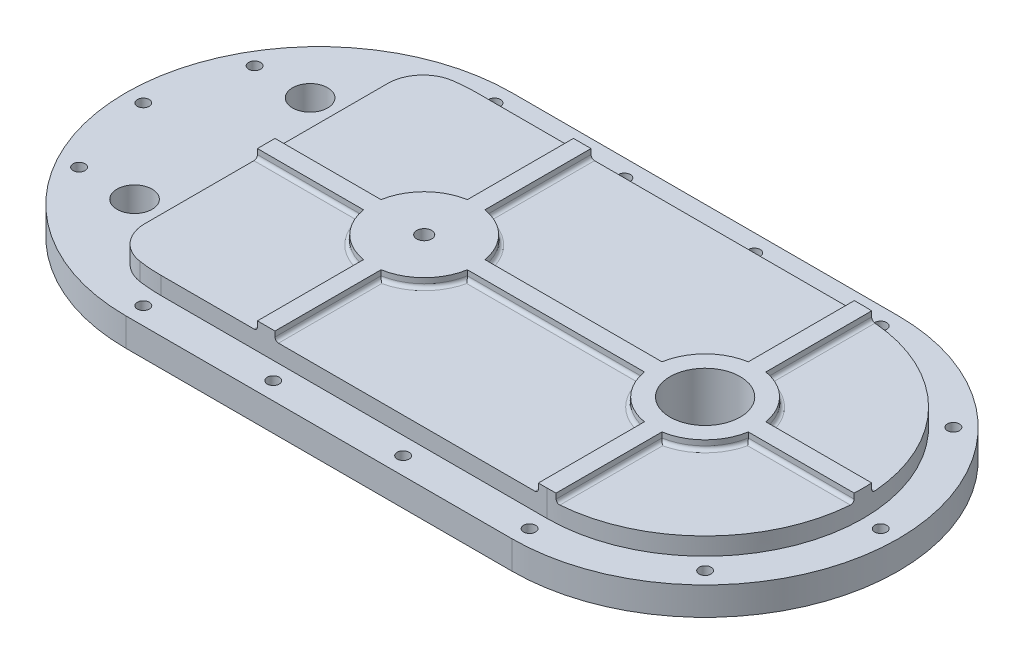
SolidWorks part; units mm, degrees
ref_plane "Front Plane" through (0, 0, 0) normal (0, 0, 1) x (1, 0, 0)
ref_plane "Top Plane" through (0, 0, 0) normal (0, 1, 0) x (1, 0, 0)
ref_plane "Right Plane" through (0, 0, 0) normal (1, 0, 0) x (0, 0, -1)
sketch "Sketch1" plane through (0, 0, 0) normal (0, 1, 0) x (1, 0, 0)
  line L0 (0, 0) -> (220, 0) construction
  line L1 (0, 110) -> (220, 110)
  line L2 (0, -110) -> (220, -110)
  arc A0 (0, 110) -> (0, -110) centre (0, 0) ccw
  arc A1 (220, -110) -> (220, 110) centre (220, 0) ccw
  point P3 (110, 0)
  dimension "D2" = 110
  dimension "D1" = 220
extrude "Boss-Extrude1" add sketch "Sketch1" along normal blind 16
sketch "Sketch2" plane through (0, 16, 0) normal (0, 1, 0) x (1, 0, 0)
  line L2 (0, 0) -> (-30, 0)
  line L3 (-30, -69.282) -> (-30, 69.282)
  line L4 (0, -90) -> (220, -90)
  line L5 (220, 90) -> (0, 90)
  line L6 (0, -90) -> (220, -90)
  line L7 (220, 90) -> (0, 90)
  arc A0 (-12.8571, -89.0769) -> (0, -90) centre (0, 0) ccw
  arc A1 (-30, -69.282) -> (-12.8571, -89.0769) centre (-10, -69.282) ccw
  arc A2 (-30, 69.282) -> (-12.8571, 89.0769) centre (-10, 69.282) cw
  arc A4 (0, 90) -> (0, -90) centre (0, 0) ccw
  arc A5 (220, -90) -> (220, 90) centre (220, 0) ccw
  arc A6 (0, 90) -> (-12.8571, 89.0769) centre (0, 0) ccw
  arc A7 (220, -90) -> (220, 90) centre (220, 0) ccw
  point P3 (-30, 0)
  point P6 (-30, -84.8528)
  dimension "D3" = 20
  dimension "D2" = 30
  dimension "D1" = 20
extrude "Boss-Extrude2" add sketch "Sketch2" along normal blind 10 contours L6 A7 L7 A6 A2 L3 A1 A0 region at (131.5227, 16, 0)
sketch "Sketch4" plane through (0, 26, 0) normal (0, 1, 0) x (1, 0, 0)
  line L0 (-30, 0) -> (310, 0) construction
  line L1 (-30, -69.282) -> (-30, 69.282) construction
  line L2 (0, 0) -> (60, 0) construction
  line L3 (60, 0) -> (220, 0) construction
  line L4 (60, -90) -> (60, 90) construction
  line L5 (0, -90) -> (220, -90) construction
  line L6 (220, 90) -> (0, 90) construction
  line L7 (220, 90) -> (220, -90) construction
  line L8 (-30, -5) -> (30.4196, -5)
  line L9 (65, -90) -> (65, -29.5804)
  line L10 (215, 90) -> (215, 29.5804)
  line L11 (-30, 5) -> (30.4196, 5)
  line L12 (55, -90) -> (55, -29.5804)
  line L13 (225, 90) -> (225, 29.5804)
  line L14 (89.5804, 5) -> (190.4196, 5)
  line L15 (-30, 5) -> (310, 5) construction
  line L16 (55, 29.5804) -> (55, 90)
  line L17 (55, -90) -> (55, 90) construction
  line L18 (89.5804, -5) -> (190.4196, -5)
  line L19 (-30, -5) -> (310, -5) construction
  line L20 (65, 29.5804) -> (65, 90)
  line L21 (65, -90) -> (65, 90) construction
  line L22 (249.5804, 5) -> (310, 5)
  line L23 (215, -29.5804) -> (215, -90)
  line L24 (215, 90) -> (215, -90) construction
  line L25 (225, -29.5804) -> (225, -90)
  line L26 (225, 90) -> (225, -90) construction
  line L27 (249.5804, -5) -> (310, -5)
  arc A0 (220, -90) -> (220, 90) centre (220, 0) ccw construction
  arc A1 (220, -90) -> (220, 90) centre (220, 0) ccw construction
  circle A2 centre (220, 0) radius 30
  circle A3 centre (60, 0) radius 30
  line M9 (-30, 69.282) -> (-30, -69.282)
  line M12 (0, -90) -> (220, -90)
  arc M13 (220, -90) -> (220, 90) centre (220, 0) ccw
  line M14 (220, 90) -> (0, 90)
  dimension "D5" = 60
  dimension "D6" = 60
  dimension "D1" = 60
  dimension "D2" = 160
  dimension "D3" = 5
  dimension "D4" = 5
extrude "Boss-Extrude3" add sketch "Sketch4" along normal blind 5 contours A3 L11 L8 M9 | A3 | A3 L20 L16 M14 | A3 L12 L9 M12 | A3 L18 A2 L14 | A2 | A2 L13 L10 M13 M14 | A2 L27 L22 M13 | A2 L23 L25 M12 M13 region at (0.0699, 26, 0) region at (60, 26, 0) region at (60, 26, 59.9301) region at (60, 26, -59.9301) region at (140, 26, 0) region at (219.9986, 26, 59.9186) region at (220, 26, 0) region at (219.9986, 26, -59.9186) region at (279.907, 26, 0)
sketch "Sketch5" plane through (0, 31, 0) normal (0, 1, 0) x (1, 0, 0)
  line L0 (0, 0) -> (220, 0) construction
  circle A0 centre (220, 0) radius 20
  dimension "D1" = 40
extrude "Cut-Extrude1" cut sketch "Sketch5" against normal through all
fillet "Fillet1" radius 2 22 edges at (55, 26, -59.7902) (38.7868, 26, -21.2132) (0.2098, 26, -5) (215, 26, -59.7902) (198.7868, 26, -21.2132) (65, 26, -59.7902) (81.2132, 26, -21.2132) (140, 26, -5) (279.7207, 26, -5) (225, 26, -59.7207) (241.2132, 26, -21.2132) (279.7207, 26, 5) (241.2132, 26, 21.2132) (225, 26, 59.7207) (198.7868, 26, 21.2132) (215, 26, 59.7902) (140, 26, 5) (81.2132, 26, 21.2132) (65, 26, 59.7902) (55, 26, 59.7902) (38.7868, 26, 21.2132) (0.2098, 26, 5)
hole_wizard "Tap Drill for M10x1.5 Tap1" positions "Sketch9" profile "Sketch7" hole size "M10x1.5" standard "ANSI Metric" end condition through all
sketch "Sketch9" plane through (0, 31, 0) normal (0, 1, 0) x (1, 0, 0)
  line L0 (220, 90) -> (0, 90) construction
  point P0 (60, 0)
  dimension "D1" = 60
  dimension "D2" = 90
sketch "Sketch7" plane through (60, 31, 0) normal (1, 0, 0) x (0, 0, 1)
  line L0 (0, 0) -> (0, 31)
  line L1 (0, 31) -> (4.25, 31)
  line L2 (4.25, 31) -> (4.25, 0)
  line L5 (4.25, 0) -> (0, 0)
  line L11 (0, -6.35) -> (0, 107.95) construction
  dimension "Thru Hole Dia." = 8.5
  dimension "Thru Hole Depth" = 31
sketch "Sketch10" plane through (0, 16, 0) normal (0, 1, 0) x (1, 0, 0)
  line L2 (-110, 0) -> (330, 0) construction
  line L4 (0, -100) -> (220, -100)
  line L5 (220, 100) -> (0, 100)
  line L6 (0, -100) -> (220, -100) construction
  line L7 (220, 100) -> (0, 100) construction
  arc A2 (0, 110) -> (0, -110) centre (0, 0) ccw construction
  arc A3 (220, -110) -> (220, 110) centre (220, 0) ccw construction
  arc A4 (0, 100) -> (0, -100) centre (0, 0) ccw
  arc A5 (220, -100) -> (220, 100) centre (220, 0) ccw
  arc A6 (0, 100) -> (0, -100) centre (0, 0) ccw construction
  arc A7 (220, -100) -> (220, 100) centre (220, 0) ccw construction
  dimension "D1" = 10
hole_wizard "Tap Drill for M8x1.25 Tap1" positions "Sketch11" profile "Sketch12" hole size "M8x1.25" standard "ANSI Metric" end condition through all
sketch "Sketch11" plane through (0, 16, 0) normal (0, 1, 0) x (1, 0, 0)
  line L0 (220, 100) -> (0, 100) construction
  line L1 (-110, 0) -> (330, 0) construction
  line L5 (220, 0) -> (297.7817, 77.7817) construction
  arc A0 (0, 100) -> (0, -100) centre (0, 0) ccw construction
  arc A1 (220, -100) -> (220, 100) centre (220, 0) ccw construction
  arc A2 (220, -110) -> (220, 110) centre (220, 0) ccw construction
  point P0 (-100, 0)
  point P5 (-86.6025, 50)
  point P7 (0, 100)
  point P10 (220, 100)
  point P13 (74, 100)
  point P17 (148, 100)
  point P19 (320, 0)
  point P44 (290.7107, 70.7107)
  point P47 (-86.6025, -50)
  point P48 (0, -100)
  point P49 (74, -100)
  point P50 (148, -100)
  point P51 (220, -100)
  point P52 (290.7107, -70.7107)
  dimension "D1" = 50
  dimension "D2" = 74
  dimension "D3" = 74
  dimension "D4" = 45
sketch "Sketch12" plane through (-100, 16, 0) normal (1, 0, 0) x (0, 0, 1)
  line L0 (0, 0) -> (0, 16)
  line L1 (0, 16) -> (3.4, 16)
  line L2 (3.4, 16) -> (3.4, 0)
  line L5 (3.4, 0) -> (0, 0)
  line L11 (0, -6.35) -> (0, 107.95) construction
  dimension "Thru Hole Dia." = 6.8
  dimension "Thru Hole Depth" = 16
sketch "Sketch13" plane through (0, 16, 0) normal (0, 1, 0) x (1, 0, 0)
  line L0 (-110, 0) -> (330, 0) construction
  circle A0 centre (-55, 50) radius 10
  circle A2 centre (-55, -50) radius 10
  dimension "D5" = 20
  dimension "D6" = 20
  dimension "D1" = 55
  dimension "D2" = 50
  dimension "D3" = 50
  dimension "D4" = 55
extrude "Cut-Extrude2" cut sketch "Sketch13" against normal through all
